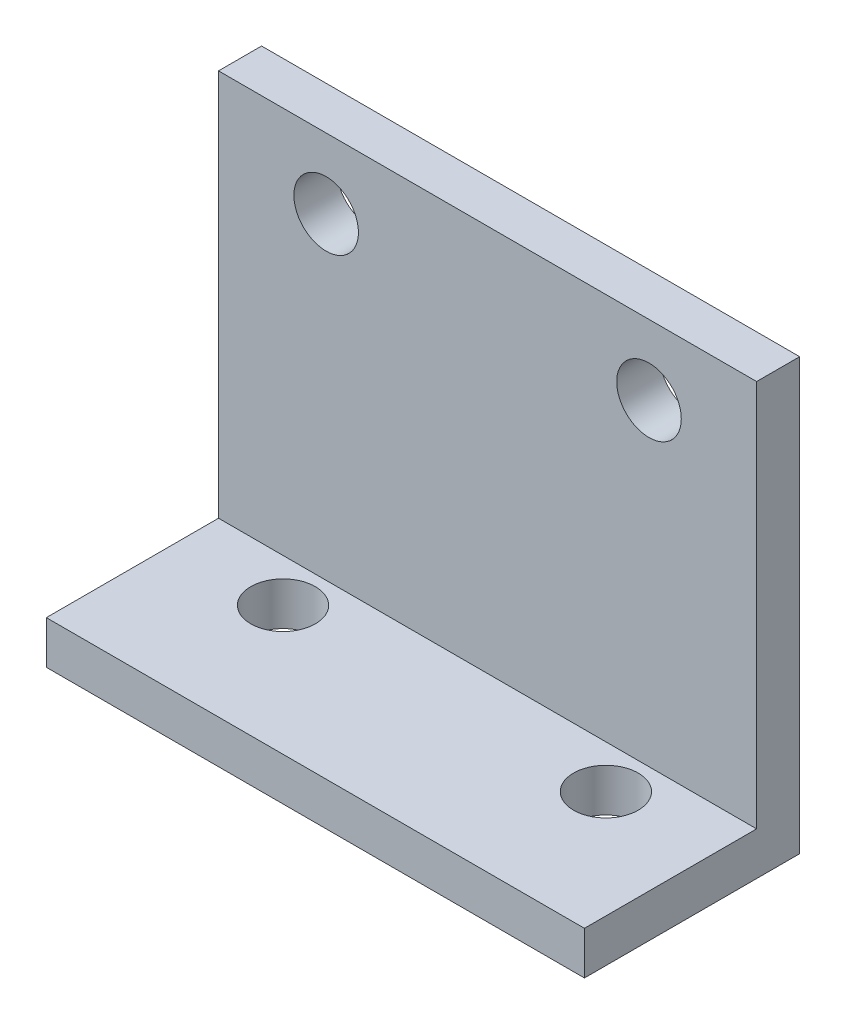
SolidWorks part; units mm, degrees
ref_plane "前视基准面" through (0, 0, 0) normal (0, 0, 1) x (1, 0, 0)
ref_plane "上视基准面" through (0, 0, 0) normal (0, 1, 0) x (1, 0, 0)
ref_plane "右视基准面" through (0, 0, 0) normal (1, 0, 0) x (0, 0, -1)
sketch "草图1" plane through (0, 0, 0) normal (0, 1, 0) x (1, 0, 0)
  line L0 (-12.5, 5) -> (-12.5, 3)
  line L1 (-12.5, 5) -> (12.5, 5)
  line L2 (-12.5, 5) -> (-12.5, -5)
  line L3 (-12.5, -5) -> (12.5, -5)
  line L4 (12.5, 5) -> (12.5, -5)
  line L5 (-12.5, 5) -> (12.5, -5) construction
  line L6 (-12.5, -5) -> (12.5, 5) construction
  line L7 (-12.5, 3) -> (12.5, 3)
  line L8 (0, 0) -> (0, -5)
  line L9 (-7.5, -5) -> (7.5, -5)
  line L10 (-7.5, -5) -> (-7.5, 0.9975)
  line L11 (-7.5, 0.9975) -> (7.5, 0.9975)
  circle A0 centre (-7.5, 0.9975) radius 1.5
  circle A1 centre (7.5, 0.9975) radius 1.5
  point P0 (0, 0)
  point P13 (0, -5)
  dimension "D1" = 25
  dimension "D2" = 10
extrude "凸台-拉伸1" add sketch "草图1" along normal blind 20 contours L0 L7 L4 L1 region at (0, 0, -4)
extrude "凸台-拉伸2" add sketch "草图1<3>" along normal blind 2 contours L7 L2 L3 L4 region at (0, 0, -2.7375)
sketch "草图1<3>" plane through (0, 0, 0) normal (0, 1, 0) x (1, 0, 0) same geometry as "草图1"
sketch "草图2" plane through (0, 0, -3) normal (0, 0, 1) x (1, 0, 0)
  line L0 (0, 2) -> (0, 20)
  line L1 (-12.5, 2) -> (12.5, 2) construction
  line L2 (-12.5, 20) -> (12.5, 20) construction
  line L3 (-7.5, 9.7381) -> (7.5, 9.7381)
  line L4 (-7.5, 9.7381) -> (-7.5, 16.7456)
  line L5 (-7.5, 16.7456) -> (7.5, 16.7456)
  circle A3 centre (-7.5, 16.7456) radius 1.5
  circle A4 centre (7.5, 16.7456) radius 1.5
  point P9 (0, 9.7381)
extrude "切除-拉伸1" cut sketch "草图2" against normal blind 2 contours L5 A3 L4 | L4 A3 L5 | A4 region at (7.5, 18.2032, -3) region at (-6.8634, 16.109, -3) region at (-7.7122, 16.9578, -3)
